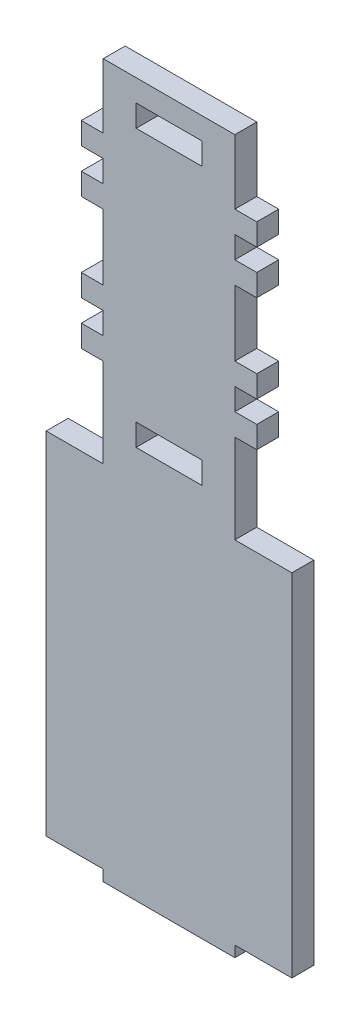
SolidWorks part; units mm, degrees
ref_plane "Front Plane" through (0, 0, 0) normal (0, 0, 1) x (1, 0, 0)
ref_plane "Top Plane" through (0, 0, 0) normal (0, 1, 0) x (1, 0, 0)
ref_plane "Right Plane" through (0, 0, 0) normal (1, 0, 0) x (0, 0, -1)
sketch "Sketch1" plane through (0, 0, 0) normal (0, 0, 1) x (1, 0, 0)
  line L0 (0, 204.7875) -> (0, 103.5307) construction
  line L1 (19.05, -1.5875) -> (-19.05, -1.5875)
  line L2 (19.05, -1.5875) -> (19.05, 1.5875)
  line L4 (-19.05, -1.5875) -> (-19.05, 1.5875)
  line L5 (19.05, -1.5875) -> (-19.05, 1.5875) construction
  line L6 (19.05, 1.5875) -> (-19.05, -1.5875) construction
  line L7 (-35.56, 1.5875) -> (-19.05, 1.5875)
  line L8 (-35.56, 1.5875) -> (-35.56, 204.7875)
  line L9 (-35.56, 204.7875) -> (35.56, 204.7875)
  line L10 (35.56, 1.5875) -> (35.56, 204.7875)
  line L11 (19.05, 1.5875) -> (35.56, 1.5875)
  line L13 (9.525, 192.0875) -> (-9.525, 192.0875)
  line L14 (9.525, 192.0875) -> (9.525, 198.4375)
  line L15 (9.525, 198.4375) -> (-9.525, 198.4375)
  line L16 (-9.525, 192.0875) -> (-9.525, 198.4375)
  line L17 (9.525, 192.0875) -> (-9.525, 198.4375) construction
  line L18 (9.525, 198.4375) -> (-9.525, 192.0875) construction
  line L19 (9.525, 112.0775) -> (-9.525, 112.0775)
  line L20 (9.525, 112.0775) -> (9.525, 118.4275)
  line L21 (9.525, 118.4275) -> (-9.525, 118.4275)
  line L22 (-9.525, 112.0775) -> (-9.525, 118.4275)
  line L23 (9.525, 112.0775) -> (-9.525, 118.4275) construction
  line L24 (9.525, 118.4275) -> (-9.525, 112.0775) construction
  point P0 (0, 0)
  point P12 (0, 195.2625)
  point P17 (0, 115.2525)
  dimension "D1" = 38.1
  dimension "D2" = 3.175
  dimension "D3" = 0
  dimension "D4" = 203.2
  dimension "D5" = 6.35
  dimension "D6" = 71.12
  dimension "D7" = 19.05
  dimension "D8" = 6.35
  dimension "D9" = 19.05
  dimension "D10" = 73.66
  dimension "D11" = 6.35
  dimension "D12" = 16.51
extrude "Boss-Extrude1" add sketch "Sketch1" along normal blind 6.35
sketch "Sketch3" plane through (0, 0, 0) normal (0, 0, -1) x (-1, 0, 0)
  line L0 (0, 204.7875) -> (0, 130.7051) construction
  line L1 (-35.56, 204.7875) -> (-19.05, 204.7875)
  line L2 (-35.56, 204.7875) -> (-35.56, 103.1875)
  line L3 (-35.56, 103.1875) -> (-19.05, 103.1875)
  line L4 (-19.05, 204.7875) -> (-19.05, 186.1084)
  line L5 (-35.56, 204.7875) -> (35.56, 204.7875) construction
  line L6 (35.56, 103.1875) -> (19.05, 103.1875)
  line L7 (19.05, 204.7875) -> (19.05, 186.1084)
  line L8 (35.56, 204.7875) -> (19.05, 204.7875)
  line L9 (35.56, 204.7875) -> (35.56, 103.1875)
  line L11 (-19.05, 128.9584) -> (-25.4, 128.9584)
  line L13 (-19.05, 135.3084) -> (-25.4, 135.3084)
  line L14 (-25.4, 128.9584) -> (-25.4, 135.3084)
  line L15 (-19.05, 141.6584) -> (-25.4, 141.6584)
  line L16 (-25.4, 141.6584) -> (-25.4, 148.0084)
  line L17 (-19.05, 148.0084) -> (-25.4, 148.0084)
  line L19 (-19.05, 186.1084) -> (-25.4, 186.1084)
  line L20 (-25.4, 179.7584) -> (-25.4, 186.1084)
  line L21 (-19.05, 179.7584) -> (-25.4, 179.7584)
  line L23 (-19.05, 167.0584) -> (-25.4, 167.0584)
  line L24 (-25.4, 167.0584) -> (-25.4, 173.4084)
  line L25 (-19.05, 173.4084) -> (-25.4, 173.4084)
  line L26 (19.05, 135.3084) -> (25.4, 135.3084)
  line L27 (25.4, 128.9584) -> (25.4, 135.3084)
  line L28 (19.05, 128.9584) -> (25.4, 128.9584)
  line L30 (19.05, 141.6584) -> (25.4, 141.6584)
  line L31 (25.4, 141.6584) -> (25.4, 148.0084)
  line L32 (19.05, 148.0084) -> (25.4, 148.0084)
  line L34 (19.05, 167.0584) -> (25.4, 167.0584)
  line L35 (25.4, 167.0584) -> (25.4, 173.4084)
  line L36 (19.05, 173.4084) -> (25.4, 173.4084)
  line L38 (19.05, 179.7584) -> (25.4, 179.7584)
  line L39 (25.4, 179.7584) -> (25.4, 186.1084)
  line L40 (19.05, 186.1084) -> (25.4, 186.1084)
  line L42 (-19.05, 179.7584) -> (-19.05, 173.4084)
  line L45 (-19.05, 167.0584) -> (-19.05, 148.0084)
  line L47 (-19.05, 141.6584) -> (-19.05, 135.3084)
  line L48 (19.05, 128.9584) -> (19.05, 103.1875)
  line L49 (19.05, 141.6584) -> (19.05, 135.3084)
  line L50 (19.05, 167.0584) -> (19.05, 148.0084)
  line L51 (19.05, 179.7584) -> (19.05, 173.4084)
  line L52 (-19.05, 128.9584) -> (-19.05, 103.1875)
  dimension "D1" = 38.1
  dimension "D2" = 6.35
  dimension "D3" = 6.35
  dimension "D4" = 2
  dimension "D5" = 2
extrude "Cut-Extrude1" cut sketch "Sketch3" against normal blind 6.35
